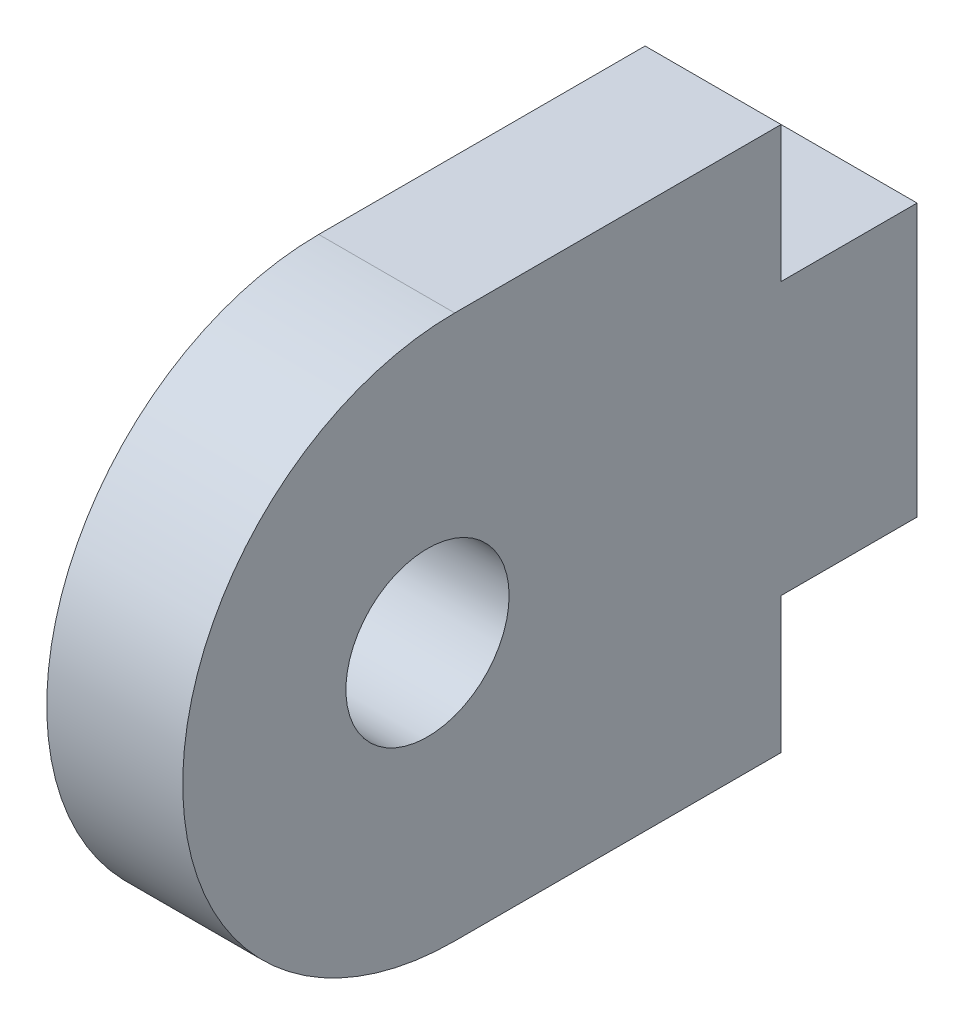
SolidWorks part; units mm, degrees
ref_plane "Front Plane" through (0, 0, 0) normal (1, 0, 0) x (0, 1, 0)
ref_plane "Top Plane" through (0, 0, 0) normal (0, 0, 1) x (0, 1, 0)
ref_plane "Right Plane" through (0, 0, 0) normal (0, 1, 0) x (-1, 0, 0)
sketch "Sketch1" plane through (0, 0, 0) normal (1, 0, 0) x (0, 1, 0)
  line L0 (0, 0) -> (0, 30096.6347) construction
  line L1 (-5, 0) -> (5, 0)
  line L2 (-5, 0) -> (-5, 5)
  line L3 (5, 0) -> (5, 5)
  line L4 (5, 5) -> (10, 5)
  line L5 (10, 5) -> (10, 27)
  line L6 (10, 27) -> (-10, 27)
  line L7 (-5, 5) -> (-10, 5)
  line L8 (-10, 5) -> (-10, 27)
  line L9 (0, 0) -> (0, 18) construction
  circle A0 centre (0, 18) radius 3
  point P6 (0, 0)
  point P13 (0, 27)
  dimension "D6" = 6
  dimension "D1" = 10
  dimension "D2" = 5
  dimension "D3" = 22
  dimension "D4" = 5
  dimension "D5" = 18
extrude "Boss-Extrude1" add sketch "Sketch1" along normal mid plane 5
fillet "Fillet1" 2 edges at (0, -10, 27) (0, 10, 27) type full round first side face at (0, -10, 16) second side face at (0, 10, 16) middle face at (0, 0, 27)
